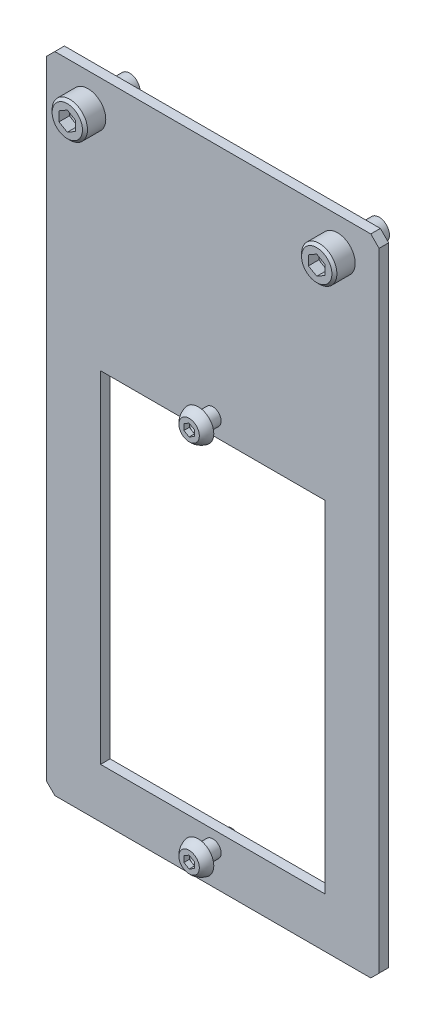
SolidWorks part; units mm, degrees
note: '?' marks a value the reader was unsure of.
ref_plane "Front Plane" through (0, 0, 0) normal (0, 0, 1) x (1, 0, 0)
ref_plane "Top Plane" through (0, 0, 0) normal (0, 1, 0) x (1, 0, 0)
ref_plane "Right Plane" through (0, 0, 0) normal (1, 0, 0) x (0, 0, -1)
ref_axis "Axis1" through (0, 14.5, 0) along (0, -1, 0)?
ref_plane "Plane1" through (0, 0, 2.3) normal (0, 0, 1) x (1, 0, 0)
sketch "Sketch1" plane through (0, 0, 0) normal (0, 0, 1) x (1, 0, 0)
  line L0 (0, 8) -> (0, -147) construction
  line L1 (-40, 0) -> (40, 0) construction
  line L2 (-40, 8) -> (40, 8)
  line L3 (-40, 8) -> (-40, -147)
  line L4 (-40, -147) -> (40, -147)
  line L5 (40, 8) -> (40, -147)
  line L6 (8.8, 0) -> (-8.8, 0) construction
  dimension "FIX_2" = 155
  dimension "FIX_3" = 80
  dimension "FIX_4" = 147
extrude "Boss-Extrude1" add sketch "Sketch1" along normal up to surface (2.3 mm away) up to plane "Plane1"
sketch "Sketch2" plane through (0, 0, 2.3) normal (0, 0, 1) x (1, 0, 0)
  line L0 (-40, 0) -> (40, 0) construction
  line L1 (0, 0) -> (0, -147) construction
  line L2 (-40, -147) -> (40, -147) construction
  line L3 (-27, -53) -> (27, -53)
  line L4 (-27, -53) -> (-27, -135)
  line L5 (-27, -135) -> (27, -135)
  line L6 (27, -53) -> (27, -135)
  circle A0 centre (-30, 0) radius 3.1
  circle A1 centre (30, 0) radius 3.1
  dimension "FIX_6" = 6.2
  dimension "FIX_5" = 60
  dimension "FIX_7" = 12
  dimension "FIX_8" = 82
  dimension "FIX_9" = 54
extrude "Cut-Extrude1" cut sketch "Sketch2" against normal through all
chamfer "Chamfer1" distance 2 4 edges at (40, -147, 1.15) (-40, -147, 1.15) (-40, 8, 1.15) (40, 8, 1.15)
sketch "Sketch3" plane through (0, 0, 0) normal (0, 1, 0) x (1, 0, 0)
  line L0 (-30, -7.3) -> (-30, 7.7) construction
  line L1 (-28, -7.3) -> (-25.75, -7.3)
  line L2 (-25.75, -7.3) -> (-25.75, -2.3)
  line L3 (-25.75, -2.3) -> (-27.5, -2.3)
  line L4 (-27.5, -2.3) -> (-27.5, 7.7)
  line L5 (-27.5, 7.7) -> (-30, 7.7)
  line L6 (-30, 7.7) -> (-30, -4.2641)
  line L8 (-27, -2.3) -> (27, -2.3) construction
  line L9 (-30, -4.2641) -> (-28, -4.8)
  line L10 (-28, -4.8) -> (-28, -7.3)
  line L11 (-30, -4.2641) -> (-32, -4.8) construction
  line L12 (-32, -4.8) -> (-28, -4.8) construction
  dimension "FIX_14" = 5
  dimension "FIX_12" = 10
  dimension "FIX_15" = 8.5
  dimension "FIX_13" = 5
  dimension "FIX_18" = 4
  dimension "FIX_16" = 2.5
  dimension "FIX_17" = 150
revolve "Revolve1" add sketch "Sketch3" angle 360 about L0
cosmetic thread "Thread1" parameters "ATD"=4.134
sketch "Sketch4" plane through (0, 0, 7.3) normal (0, 0, 1) x (1, 0, 0)
  line L0 (0, -8.25) -> (0, 8.25) construction
  line L1 (-30, 2.3094) -> (-32, 1.1547)
  line L2 (-32, 1.1547) -> (-32, -1.1547)
  line L3 (-32, -1.1547) -> (-30, -2.3094)
  line L4 (-30, -2.3094) -> (-28, -1.1547)
  line L5 (-28, -1.1547) -> (-28, 1.1547)
  line L6 (-28, 1.1547) -> (-30, 2.3094)
  circle A0 centre (-30, 0) radius 2 construction
  dimension "FIX_20" = 4
extrude "Cut-Extrude2" cut sketch "Sketch4" against normal blind 2.5
chamfer "Chamfer2" distance 0.6 1 edges at (-25.75, 0, 7.3)
mirror "Mirror1" about plane through (0, 0, 0) normal (1, 0, 0) of "Chamfer2", "Revolve1", "Cut-Extrude2"
ref_plane "Plane2" through (0, 0, 5.8) normal (0, 0, 1) x (1, 0, 0)
sketch "Sketch5" plane through (0, 0, 0) normal (1, 0, 0) x (0, 0, -1)
  line L0 (-8, -49) -> (2.2, -49) construction
  line L1 (-5.8, 44) -> (-5.8, -44) construction
  line L2 (2.2, -47) -> (-5.8, -47)
  line L3 (-5.8, -47) -> (-5.8, -45.265)
  line L4 (-8, -46.5444) -> (-8, -47.75)
  line L5 (-5.8, -49) -> (-5.8, -47) construction
  line L6 (-8, -47.75) -> (-6.7, -47.75)
  line L7 (-5.9783, -49) -> (2.2, -49)
  line L8 (2.2, -49) -> (2.2, -47)
  line L9 (-8, -49) -> (2.2, -49) construction
  line L10 (-6.7, -47.75) -> (-5.9783, -49)
  line L11 (-5.9783, -49) -> (-6.7, -50.25) construction
  line L12 (-6.7, -50.25) -> (-6.7, -47.75) construction
  line L13 (8.25, 0) -> (-8.25, 0) construction
  arc A0 (-5.8, -45.265) -> (-8, -46.5444) centre (-5.1, -49) ccw
  dimension "FIX_31" = 3.8
  dimension "FIX_24" = 4
  dimension "FIX_25" = 8
  dimension "FIX_26" = 2.2
  dimension "FIX_27" = 1.3
  dimension "FIX_28" = 120
  dimension "FIX_29" = 2.5
  dimension "FIX_30" = 0.7
  dimension "FIX_32" = 49
revolve "Revolve2" add sketch "Sketch5" angle 360 about L0
cosmetic thread "Thread2" parameters "ATD"=3.242
sketch "Sketch6" plane through (0, 0, 8) normal (0, 0, 1) x (1, 0, 0)
  line L1 (0, -47.5566) -> (-1.25, -48.2783)
  line L2 (-1.25, -48.2783) -> (-1.25, -49.7217)
  line L3 (-1.25, -49.7217) -> (0, -50.4434)
  line L4 (0, -50.4434) -> (1.25, -49.7217)
  line L5 (1.25, -49.7217) -> (1.25, -48.2783)
  line L6 (1.25, -48.2783) -> (0, -47.5566)
  line L7 (0, -8.25) -> (0, 8.25) construction
  circle A0 centre (0, -49) radius 1.25 construction
  dimension "FIX_34" = 2.5
extrude "Cut-Extrude3" cut sketch "Sketch6" against normal blind 1.3
pattern_linear "LPattern1" count 2 spacing 90 along (0, -1, 0) of "Revolve2", "Cut-Extrude3"
